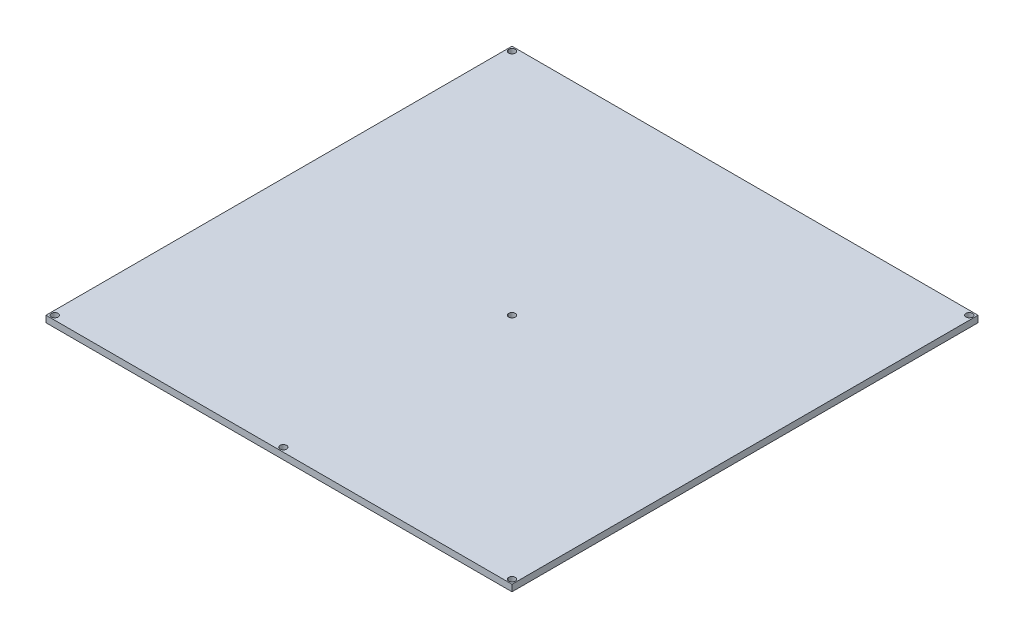
SolidWorks part; units mm, degrees
ref_plane "Front Plane" through (0, 0, 0) normal (0, 0, 1) x (1, 0, 0)
ref_plane "Top Plane" through (0, 0, 0) normal (0, 1, 0) x (1, 0, 0)
ref_plane "Right Plane" through (0, 0, 0) normal (1, 0, 0) x (0, 0, -1)
sketch "Sketch1" plane through (0, 0, 0) normal (0, 1, 0) x (1, 0, 0)
  line L0 (104.5, -104.5) -> (-104.5, -104.5) construction
  line L1 (-106.5, -106.5) -> (106.5, -106.5)
  line L2 (-106.5, -106.5) -> (-106.5, 106.5)
  line L3 (-106.5, 106.5) -> (106.5, 106.5)
  line L4 (106.5, -106.5) -> (106.5, 106.5)
  line L5 (-106.5, -106.5) -> (106.5, 106.5) construction
  line L6 (-106.5, 106.5) -> (106.5, -106.5) construction
  line L7 (-104.5, 104.5) -> (104.5, 104.5) construction
  line L8 (0, 0) -> (0, -106.5) construction
  circle A0 centre (-104.5, 104.5) radius 1.5
  circle A1 centre (104.5, 104.5) radius 1.5
  circle A2 centre (-104.5, -104.5) radius 1.5
  circle A3 centre (104.5, -104.5) radius 1.5
  circle A4 centre (0, 0) radius 1.5
  circle A5 centre (0, -104.5) radius 1.5
  point P0 (0, 0)
  point P18 (0, 0.1379)
  point P20 (0, -104.5)
  dimension "D2" = 3
  dimension "D1" = 213
  dimension "D3" = 209
extrude "Boss-Extrude1" add sketch "Sketch1" along normal blind 3
